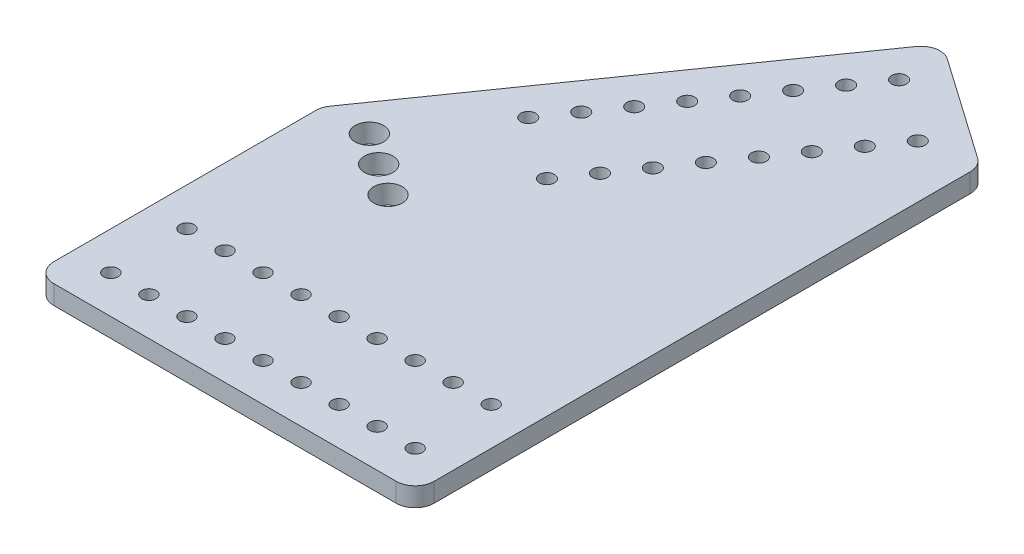
SolidWorks part; units mm, degrees
material "6061-T6 (SS)"
ref_plane "Front Plane" through (0, 0, 0) normal (0, 0, 1) x (1, 0, 0)
ref_plane "Top Plane" through (0, 0, 0) normal (0, 1, 0) x (1, 0, 0)
ref_plane "Right Plane" through (0, 0, 0) normal (1, 0, 0) x (0, 0, -1)
sketch "Sketch1" plane through (0, 0, 0) normal (0, 1, 0) x (1, 0, 0)
  line L0 (0, 95.8127) -> (85.3871, 217.7581)
  line L5 (0, 0) -> (127, 0)
  line L6 (0, 0) -> (0, 95.8127)
  line L7 (85.3871, 217.7581) -> (127, 217.7581) construction
  line L8 (127, 0) -> (127, 188.6204)
  line L9 (85.3871, 217.7581) -> (127, 188.6204)
  line L10 (127, 188.6204) -> (127, 217.7581) construction
  line L11 (0, 0) -> (-12.7, 0) construction
  line L12 (-12.7, 0) -> (-12.7, 77.6752) construction
  line L13 (0, 95.8127) -> (41.6129, 66.675) construction
  line L14 (0, 95.8127) -> (85.3871, 217.7581) construction
  line L15 (41.6129, 66.675) -> (127, 188.6204) construction
  line L16 (85.3871, 217.7581) -> (127, 188.6204) construction
  point P2 (70.2931, 199.8216)
  point P10 (0, 0)
  dimension "D1" = 66.675
  dimension "D2" = 127
  dimension "D3" = 55
  dimension "D4" = 50.8
  dimension "D5" = 12.7
  dimension "D6" = 12.7
extrude "Boss-Extrude1" add sketch "Sketch1" along normal blind 6.35
sketch "Sketch2" plane through (0, 6.35, 0) normal (0, 1, 0) x (1, 0, 0)
  line L0 (0, 0) -> (127, 0) construction
  line L1 (0, 95.8127) -> (0, 0) construction
  line L2 (88.5059, 200.0704) -> (109.3123, 185.5016) construction
  line L3 (127, 188.6204) -> (85.3871, 217.7581) construction
  line L4 (85.3871, 217.7581) -> (0, 95.8127) construction
  line L5 (15.6617, 96.0381) -> (36.4681, 81.4693) construction
  line L6 (36.4681, 81.4693) -> (58.3214, 112.679) construction
  circle A0 centre (12.7, 12.7) radius 2.413
  circle A2 centre (12.7, 38.1) radius 2.413
  circle A3 centre (25.4, 38.1) radius 2.413
  circle A4 centre (38.1, 38.1) radius 2.413
  circle A5 centre (50.8, 38.1) radius 2.413
  circle A6 centre (63.5, 38.1) radius 2.413
  circle A7 centre (25.4, 12.7) radius 2.413
  circle A8 centre (38.1, 12.7) radius 2.413
  circle A9 centre (50.8, 12.7) radius 2.413
  circle A10 centre (63.5, 12.7) radius 2.413
  circle A11 centre (76.2, 12.7) radius 2.413
  circle A12 centre (76.2, 38.1) radius 2.413
  circle A13 centre (88.9, 12.7) radius 2.413
  circle A14 centre (88.9, 38.1) radius 2.413
  circle A15 centre (101.6, 12.7) radius 2.413
  circle A16 centre (101.6, 38.1) radius 2.413
  circle A21 centre (88.5059, 200.0704) radius 2.4892
  circle A22 centre (109.3123, 185.5016) radius 2.4892
  circle A23 centre (81.2215, 189.6672) radius 2.4892
  circle A24 centre (102.0279, 175.0983) radius 2.4892
  circle A25 centre (73.937, 179.264) radius 2.4892
  circle A26 centre (94.7435, 164.6951) radius 2.4892
  circle A27 centre (66.6526, 168.8607) radius 2.4892
  circle A28 centre (87.4591, 154.2919) radius 2.4892
  circle A29 centre (59.3682, 158.4575) radius 2.4892
  circle A30 centre (80.1747, 143.8886) radius 2.4892
  circle A31 centre (52.0838, 148.0543) radius 2.4892
  circle A32 centre (72.8902, 133.4854) radius 2.4892
  circle A33 centre (44.7994, 137.651) radius 2.4892
  circle A34 centre (65.6058, 123.0822) radius 2.4892
  circle A35 centre (37.5149, 127.2478) radius 2.4892
  circle A36 centre (58.3214, 112.679) radius 2.4892
  circle A37 centre (15.6617, 96.0381) radius 4.7625
  circle A38 centre (26.0649, 88.7537) radius 4.7625
  circle A39 centre (36.4681, 81.4693) radius 4.7625
  circle A40 centre (114.3, 12.7) radius 2.413
  circle A41 centre (114.3, 38.1) radius 2.413
  dimension "D1" = 4.826
  dimension "D2" = 12.7
  dimension "D3" = 12.7
  dimension "D6" = 25.4
  dimension "D7" = 12.7
  dimension "D8" = 12.7
  dimension "D9" = 4.9784
  dimension "D15" = 9.525
  dimension "D10" = 12.7
  dimension "D11" = 25.4
  dimension "D12" = 12.7
  dimension "D13" = 8
  dimension "D14" = 38.1
  dimension "D4" = 2
  dimension "D5" = 9
extrude "Cut-Extrude1" cut sketch "Sketch2" against normal through all
fillet "Fillet1" radius 6.35 5 edges at (85.3871, 3.175, -217.7581) (127, 3.175, -188.6204) (127, 3.175, 0) (0, 3.175, 0) (0, 3.175, -95.8127)
